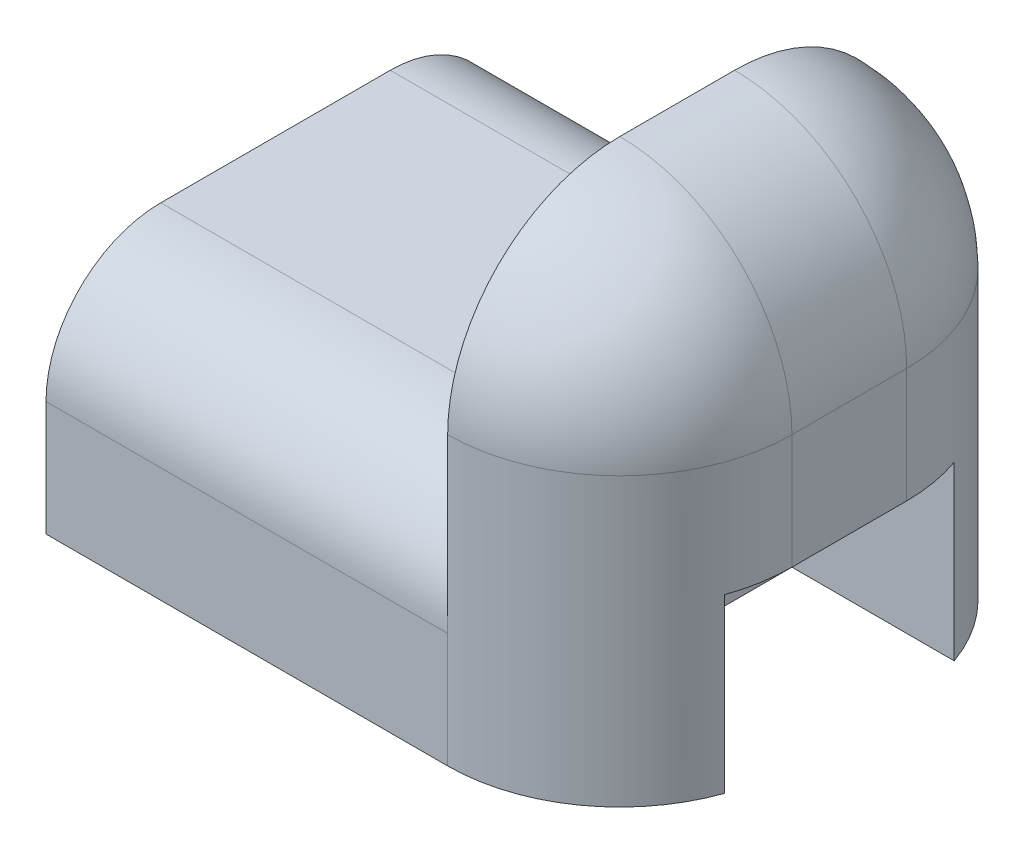
SolidWorks part; units mm, degrees
ref_plane "前基準面" through (0, 0, 0) normal (0, 0, 1) x (1, 0, 0)
ref_plane "上基準面" through (0, 0, 0) normal (0, 1, 0) x (1, 0, 0)
ref_plane "右基準面" through (0, 0, 0) normal (1, 0, 0) x (0, 0, -1)
sketch "草圖1" plane through (0, 0, 0) normal (0, 1, 0) x (1, 0, 0)
  line L1 (-50, 20) -> (50, 20)
  line L2 (-50, 20) -> (-50, -20)
  line L3 (-50, -20) -> (50, -20)
  line L4 (50, 20) -> (50, -20)
  line L5 (-50, 20) -> (50, -20) construction
  line L6 (-50, -20) -> (50, 20) construction
  point P0 (0, 0)
  dimension "D1" = 100
  dimension "D2" = 40
extrude "填料-伸長1" add sketch "草圖1" along normal blind 80
sketch "草圖3" plane through (0, 0, 20) normal (0, 0, 1) x (1, 0, 0)
  line L0 (0, 80) -> (0, 0)
  line L1 (50, 0) -> (20, 0)
  line L2 (50, 0) -> (50, 30)
  line L3 (50, 30) -> (20, 30)
  line L4 (20, 0) -> (20, 30)
  line L5 (-50, 80) -> (50, 80) construction
  line L6 (-50, 0) -> (-20, 0)
  line L7 (-50, 0) -> (-50, 30)
  line L8 (-50, 30) -> (-20, 30)
  line L9 (-20, 0) -> (-20, 30)
  line M3 (-50, 0) -> (50, 0)
  line M4 (50, 0) -> (50, 80)
  line M6 (-50, 80) -> (-50, 0)
  dimension "D1" = 30
  dimension "D2" = 30
extrude "除料-伸長2" cut sketch "草圖3" against normal blind 20 contours L9 L8 M3 M6 | L4 L3 M3 M4 region at (-35, 15, 20) region at (35, 15, 20)
ref_plane "平面1" through (0, 0, 0) normal (0, 0, 1) x (1, 0, 0)
sketch "草圖6" plane through (0, 0, 0) normal (0, 0, 1) x (1, 0, 0)
  line L0 (-50, 0) -> (-20, 0) construction
  line L1 (-50, 30) -> (-50, 0) construction
  line L2 (0, 80) -> (0, 0)
  line L3 (-50, 80) -> (50, 80) construction
  circle A0 centre (-43, 7) radius 5
  dimension "D1" = 10
  dimension "D2" = 7
  dimension "D3" = 7
extrude "填料-伸長2" add sketch "草圖6" along normal blind 20 contours A0 region at (-43, 7, 0)
mirror "鏡射3" about plane through (-50, 80, 20) normal (0, 0, -1) of "填料-伸長2", "除料-伸長2", "填料-伸長1"
sketch "草圖7" plane through (0, 80, 0) normal (0, 1, 0) x (1, 0, 0)
  line L0 (50, -60) -> (-50, -60) construction
  line L1 (-50, 20) -> (20, 20)
  line L2 (-50, 20) -> (-50, -60)
  line L3 (-50, -60) -> (20, -60)
  line L4 (20, 20) -> (20, -60)
  dimension "D1" = 70
extrude "除料-伸長3" cut sketch "草圖7" against normal blind 40
fillet "圓角1" radius 30 1 edges at (50, 80, 20)
fillet "圓角2" radius 30 2 edges at (50, 25, 60) (41.2132, 71.2132, 60)
fillet "圓角3" radius 30 2 edges at (50, 25, -20) (41.2132, 71.2132, -20)
fillet "圓角4" radius 20 1 edges at (-15, 40, 60)
fillet "圓角5" radius 20 1 edges at (-15, 40, -20)
sketch "草圖8" plane through (0, 0, 60) normal (0, 0, 1) x (1, 0, 0)
  line L0 (20, 0) -> (-50, 0) construction
  line L1 (20, 0) -> (20, 20) construction
  circle A0 centre (-15, 10) radius 5
  dimension "D1" = 10
  dimension "D2" = 10
  dimension "D3" = 35
sketch "Sketch1" plane through (0, 30, 0) normal (0, -1, 0) x (1, 0, 0)
  line L0 (48.2843, 40) -> (20, 40) construction
  line L1 (20, 0) -> (20, 40) construction
  circle A0 centre (43, 20) radius 5
  dimension "D1" = 10
  dimension "D2" = 20
  dimension "D3" = 23
extrude "Cut-Extrude1" cut sketch "Sketch1" against normal blind 5
